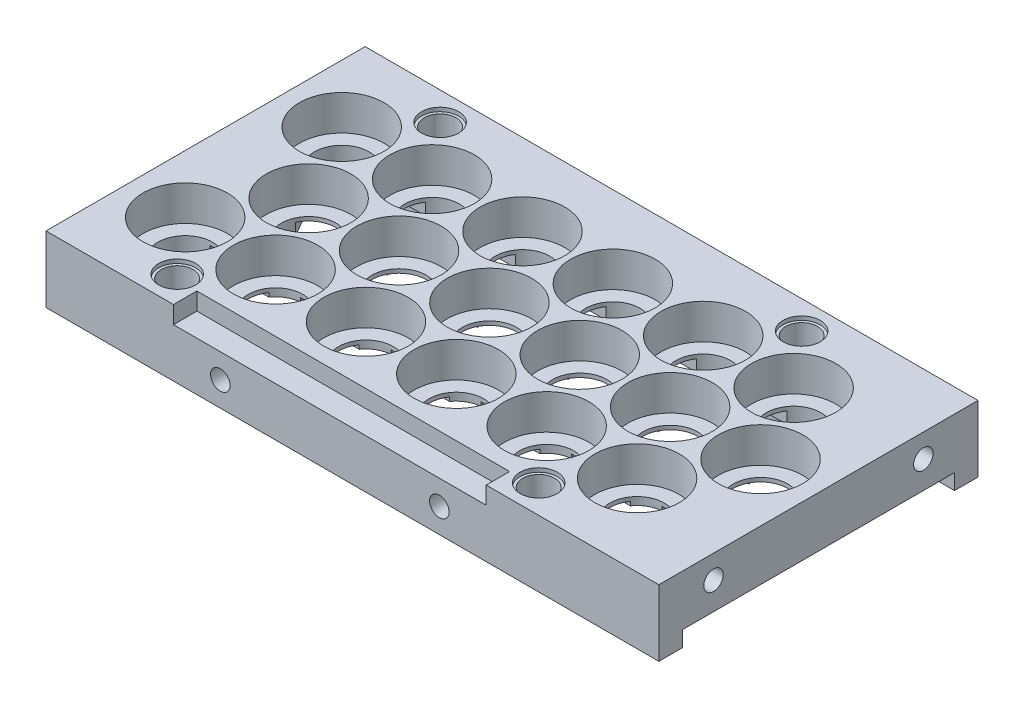
SolidWorks part; units mm, degrees
ref_plane "Front Plane" through (0, 0, 0) normal (0, 0, 1) x (1, 0, 0)
ref_plane "Top Plane" through (0, 0, 0) normal (0, 1, 0) x (1, 0, 0)
ref_plane "Right Plane" through (0, 0, 0) normal (1, 0, 0) x (0, 0, -1)
sketch "Sketch1" plane through (0, 0, 0) normal (0, 1, 0) x (1, 0, 0)
  line L0 (0, 0) -> (11.575, -20.0485) construction
  line L1 (11.575, -20.0485) -> (0, -40.097) construction
  line L2 (0, 0) -> (11.575, 0) construction
  line L3 (11.575, 0) -> (11.575, -20.0485) construction
  line L4 (11.575, -20.0485) -> (11.575, -40.097) construction
  line L5 (11.575, -40.097) -> (0, -40.097) construction
  line L6 (0, 0) -> (23.15, 0) construction
  line L7 (0, 0) -> (23.15, 0) construction
  line L8 (-14.825, -60.922) -> (142.15, -60.922)
  line L9 (-14.825, -60.922) -> (-14.825, 20.825)
  line L10 (-14.825, 20.825) -> (142.15, 20.825)
  line L11 (142.15, -60.922) -> (142.15, 20.825)
  circle A0 centre (0, 0) radius 10.825
  circle A1 centre (11.575, -20.0485) radius 10.825
  circle A2 centre (0, -40.097) radius 10.825
  circle A3 centre (23.15, 0) radius 10.825
  circle A4 centre (34.725, -20.0485) radius 10.825
  circle A5 centre (23.15, -40.097) radius 10.825
  circle A6 centre (46.3, 0) radius 10.825
  circle A7 centre (57.875, -20.0485) radius 10.825
  circle A8 centre (46.3, -40.097) radius 10.825
  circle A9 centre (69.45, 0) radius 10.825
  circle A10 centre (81.025, -20.0485) radius 10.825
  circle A11 centre (69.45, -40.097) radius 10.825
  circle A12 centre (92.6, 0) radius 10.825
  circle A13 centre (104.175, -20.0485) radius 10.825
  circle A14 centre (92.6, -40.097) radius 10.825
  circle A15 centre (115.75, 0) radius 10.825
  circle A16 centre (127.325, -20.0485) radius 10.825
  circle A17 centre (115.75, -40.097) radius 10.825
  circle A18 centre (0, 0) radius 7
  circle A19 centre (11.575, -20.0485) radius 7
  circle A20 centre (0, -40.097) radius 7
  circle A21 centre (23.15, 0) radius 7
  circle A22 centre (34.725, -20.0485) radius 7
  circle A23 centre (23.15, -40.097) radius 7
  circle A24 centre (46.3, 0) radius 7
  circle A25 centre (57.875, -20.0485) radius 7
  circle A26 centre (46.3, -40.097) radius 7
  circle A27 centre (69.45, 0) radius 7
  circle A28 centre (81.025, -20.0485) radius 7
  circle A29 centre (69.45, -40.097) radius 7
  circle A30 centre (92.6, 0) radius 7
  circle A31 centre (104.175, -20.0485) radius 7
  circle A32 centre (92.6, -40.097) radius 7
  circle A33 centre (115.75, 0) radius 7
  circle A34 centre (127.325, -20.0485) radius 7
  circle A35 centre (115.75, -40.097) radius 7
  dimension "D3" = 21.65
  dimension "D11" = 14
  dimension "D1" = 60
  dimension "D2" = 60
  dimension "D4" = 1.5
  dimension "D6" = 23.15
  dimension "D7" = 4
  dimension "D8" = 4
  dimension "D9" = 10
  dimension "D10" = 10
  dimension "D13" = 23.15
  dimension "D5" = 6
  dimension "D12" = 6
extrude "Boss-Extrude2" add sketch "Sketch1" along normal blind 11 contours L8 L11 L10 L9 A17 A16 A15 A14 A13 A12 A11 A10 A9 A8 A7 A6 A5 A4 A3 A2 A1 A0 region at (-13.0551, 0, 20.0485)
extrude "Boss-Extrude3" add sketch "Sketch1<3>" along normal blind 2 contours A0 A18 | A3 A21 | A6 A24 | A9 A27 | A12 A30 | A15 A33 | A1 A19 | A4 A22 | A7 A25 | A10 A28 | A13 A31 | A16 A34 | A17 A35 | A14 A32 | A11 A29 | A8 A26 | A5 A23 | A2 A20 region at (-10.5188, 0, 0) region at (1.0562, 0, 20.0485) region at (-10.5188, 0, 40.097) region at (12.6312, 0, 0) region at (24.2062, 0, 20.0485) region at (12.6312, 0, 40.097) region at (35.7812, 0, 0) region at (47.3562, 0, 20.0485) region at (35.7812, 0, 40.097) region at (58.9312, 0, 0) region at (70.5062, 0, 20.0485) region at (58.9312, 0, 40.097) region at (82.0812, 0, 0) region at (93.6562, 0, 20.0485) region at (82.0812, 0, 40.097) region at (105.2312, 0, 0) region at (116.8062, 0, 20.0485) region at (105.2312, 0, 40.097)
sketch "Sketch1<3>" plane through (0, 0, 0) normal (0, 1, 0) x (1, 0, 0) same geometry as "Sketch1"
sketch "Sketch2" plane through (0, 0, 0) normal (0, -1, 0) x (1, 0, 0)
  line L0 (0, 40.097) -> (11.575, 20.0485) construction
  line L1 (3.4641, 42.097) -> (15.0391, 22.0485)
  line L2 (-3.4641, 38.097) -> (8.1109, 18.0485)
  line L3 (11.575, 20.0485) -> (0, 0) construction
  line L4 (15.0391, 18.0485) -> (3.4641, -2)
  line L5 (8.1109, 22.0485) -> (-3.4641, 2)
  line L6 (19.6859, 38.097) -> (31.2609, 18.0485)
  line L7 (26.6141, 42.097) -> (38.1891, 22.0485)
  line L8 (31.2609, 22.0485) -> (19.6859, 2)
  line L9 (38.1891, 18.0485) -> (26.6141, -2)
  line L10 (23.15, 40.097) -> (34.725, 20.0485) construction
  line L11 (34.725, 20.0485) -> (23.15, 0) construction
  line L12 (42.8359, 38.097) -> (54.4109, 18.0485)
  line L13 (49.7641, 42.097) -> (61.3391, 22.0485)
  line L14 (54.4109, 22.0485) -> (42.8359, 2)
  line L15 (61.3391, 18.0485) -> (49.7641, -2)
  line L16 (46.3, 40.097) -> (57.875, 20.0485) construction
  line L17 (57.875, 20.0485) -> (46.3, 0) construction
  line L18 (65.9859, 38.097) -> (77.5609, 18.0485)
  line L19 (72.9141, 42.097) -> (84.4891, 22.0485)
  line L20 (77.5609, 22.0485) -> (65.9859, 2)
  line L21 (84.4891, 18.0485) -> (72.9141, -2)
  line L22 (69.45, 40.097) -> (81.025, 20.0485) construction
  line L23 (81.025, 20.0485) -> (69.45, 0) construction
  line L24 (89.1359, 38.097) -> (100.7109, 18.0485)
  line L25 (96.0641, 42.097) -> (107.6391, 22.0485)
  line L26 (100.7109, 22.0485) -> (89.1359, 2)
  line L27 (107.6391, 18.0485) -> (96.0641, -2)
  line L28 (92.6, 40.097) -> (104.175, 20.0485) construction
  line L29 (104.175, 20.0485) -> (92.6, 0) construction
  line L30 (112.2859, 38.097) -> (123.8609, 18.0485)
  line L31 (119.2141, 42.097) -> (130.7891, 22.0485)
  line L32 (123.8609, 22.0485) -> (112.2859, 2)
  line L33 (130.7891, 18.0485) -> (119.2141, -2)
  line L34 (115.75, 40.097) -> (127.325, 20.0485) construction
  line L35 (127.325, 20.0485) -> (115.75, 0) construction
  line L36 (-3.4641, 38.097) -> (19.6859, 38.097) construction
  line L37 (0, 40.097) -> (115.75, 40.097) construction
  line L38 (0, 44.097) -> (115.75, 44.097)
  line L39 (0, 36.097) -> (115.75, 36.097)
  line L40 (11.575, 20.0485) -> (127.325, 20.0485) construction
  line L41 (11.575, 24.0485) -> (127.325, 24.0485)
  line L42 (11.575, 16.0485) -> (127.325, 16.0485)
  line L43 (0, 0) -> (115.75, 0) construction
  line L44 (0, 4) -> (115.75, 4)
  line L45 (0, -4) -> (115.75, -4)
  arc A0 (3.4641, 42.097) -> (-3.4641, 38.097) centre (0, 40.097) ccw
  arc A1 (8.1109, 18.0485) -> (15.0391, 22.0485) centre (11.575, 20.0485) ccw
  arc A2 (15.0391, 18.0485) -> (8.1109, 22.0485) centre (11.575, 20.0485) ccw
  arc A3 (-3.4641, 2) -> (3.4641, -2) centre (0, 0) ccw
  arc A4 (26.6141, 42.097) -> (19.6859, 38.097) centre (23.15, 40.097) ccw
  arc A5 (31.2609, 18.0485) -> (38.1891, 22.0485) centre (34.725, 20.0485) ccw
  arc A6 (38.1891, 18.0485) -> (31.2609, 22.0485) centre (34.725, 20.0485) ccw
  arc A7 (19.6859, 2) -> (26.6141, -2) centre (23.15, 0) ccw
  arc A8 (49.7641, 42.097) -> (42.8359, 38.097) centre (46.3, 40.097) ccw
  arc A9 (54.4109, 18.0485) -> (61.3391, 22.0485) centre (57.875, 20.0485) ccw
  arc A10 (61.3391, 18.0485) -> (54.4109, 22.0485) centre (57.875, 20.0485) ccw
  arc A11 (42.8359, 2) -> (49.7641, -2) centre (46.3, 0) ccw
  arc A12 (72.9141, 42.097) -> (65.9859, 38.097) centre (69.45, 40.097) ccw
  arc A13 (77.5609, 18.0485) -> (84.4891, 22.0485) centre (81.025, 20.0485) ccw
  arc A14 (84.4891, 18.0485) -> (77.5609, 22.0485) centre (81.025, 20.0485) ccw
  arc A15 (65.9859, 2) -> (72.9141, -2) centre (69.45, 0) ccw
  arc A16 (96.0641, 42.097) -> (89.1359, 38.097) centre (92.6, 40.097) ccw
  arc A17 (100.7109, 18.0485) -> (107.6391, 22.0485) centre (104.175, 20.0485) ccw
  arc A18 (107.6391, 18.0485) -> (100.7109, 22.0485) centre (104.175, 20.0485) ccw
  arc A19 (89.1359, 2) -> (96.0641, -2) centre (92.6, 0) ccw
  arc A20 (119.2141, 42.097) -> (112.2859, 38.097) centre (115.75, 40.097) ccw
  arc A21 (123.8609, 18.0485) -> (130.7891, 22.0485) centre (127.325, 20.0485) ccw
  arc A22 (130.7891, 18.0485) -> (123.8609, 22.0485) centre (127.325, 20.0485) ccw
  arc A23 (112.2859, 2) -> (119.2141, -2) centre (115.75, 0) ccw
  arc A24 (0, 44.097) -> (0, 36.097) centre (0, 40.097) ccw
  arc A25 (115.75, 36.097) -> (115.75, 44.097) centre (115.75, 40.097) ccw
  arc A26 (11.575, 24.0485) -> (11.575, 16.0485) centre (11.575, 20.0485) ccw
  arc A27 (127.325, 16.0485) -> (127.325, 24.0485) centre (127.325, 20.0485) ccw
  arc A28 (0, 4) -> (0, -4) centre (0, 0) ccw
  arc A29 (115.75, -4) -> (115.75, 4) centre (115.75, 0) ccw
  point P3 (5.7875, 30.0727)
  point P8 (5.7875, 10.0242)
  point P18 (28.9375, 30.0727)
  point P25 (28.9375, 10.0242)
  point P34 (52.0875, 30.0727)
  point P39 (52.0875, 10.0242)
  point P48 (75.2375, 30.0727)
  point P53 (75.2375, 10.0242)
  point P62 (98.3875, 30.0727)
  point P67 (98.3875, 10.0242)
  point P76 (121.5375, 30.0727)
  point P81 (121.5375, 10.0242)
  point P91 (57.875, 40.097)
  point P96 (69.45, 20.0485)
  point P103 (57.875, 0)
  circle M62 centre (0, 0) radius 7
  circle M63 centre (23.15, 0) radius 7
  circle M64 centre (46.3, 0) radius 7
  circle M65 centre (69.45, 0) radius 7
  circle M66 centre (92.6, 0) radius 7
  circle M67 centre (115.75, 0) radius 7
  circle M68 centre (11.575, 20.0485) radius 7
  circle M69 centre (34.725, 20.0485) radius 7
  circle M70 centre (57.875, 20.0485) radius 7
  circle M71 centre (81.025, 20.0485) radius 7
  circle M72 centre (104.175, 20.0485) radius 7
  circle M73 centre (127.325, 20.0485) radius 7
  circle M74 centre (115.75, 40.097) radius 7
  circle M75 centre (92.6, 40.097) radius 7
  circle M76 centre (69.45, 40.097) radius 7
  circle M77 centre (46.3, 40.097) radius 7
  circle M78 centre (23.15, 40.097) radius 7
  circle M79 centre (0, 40.097) radius 7
  dimension "D1" = 8
  dimension "D3" = 23.15
  dimension "D4" = 8
  dimension "D5" = 8
  dimension "D6" = 8
extrude "Cut-Extrude1" cut sketch "Sketch2" against normal blind 1 contours L1 L39 L38 M78 M79 | L7 L39 L38 M77 M78 | L39 L2 L1 M79 M68 | L42 L8 L6 L41 M68 M69 | L6 L41 L7 L39 M69 M78 | L12 L41 L13 L39 M70 M77 | L13 L39 L38 M76 M77 | L18 L41 L19 L39 M71 M76 | L19 L39 L38 M75 M76 | L24 L41 L25 L39 M72 M75 | L25 L39 L38 M74 M75 | L30 L41 L31 M73 M74 | L42 L32 L30 L41 M72 M73 | L42 L26 L24 L41 M71 M72 | L42 L20 L18 L41 M70 M71 | L42 L14 L12 L41 M69 M70 | L45 L44 L4 M62 M63 | L44 L4 L5 M62 M68 | L45 L44 L9 M63 M64 | L45 L44 L15 M64 M65 | L45 L44 L21 M65 M66 | L45 L44 L27 M66 M67 | L44 L27 L42 L26 M66 M72 | L42 L32 L33 M67 M73 | L44 L21 L42 L20 M65 M71 | L44 L15 L42 L14 M64 M70 | L39 L13 M77 | L39 L25 M75 | L39 L19 M76 | L41 L6 M69 | L44 L4 M62 | L44 L15 M64 | L44 L21 M65 | L44 L27 M66 | L41 L30 M73 | L32 L42 M73 | L41 L24 M72 | L26 L42 M72 | L41 L18 M71 | L20 L42 M71 | L41 L12 M70 | L14 L42 M70 | L44 L9 L42 L8 M63 M69 | L8 L42 M69 | L39 L7 M78 | L39 L1 M79 | L44 A29 L45 A28 region at (11.6138, 0, 40.1242) region at (6.3461, 0, 36.4331) region at (5.7834, 0, 30.0255) region at (23.0718, 0, 20.0485) region at (28.9375, 0, 30.0727) region at (34.7638, 0, 40.1242) region at (28.3789, 0, 23.7124) region at (5.7834, 0, 10.0715) region at (29.4961, 0, 36.4331) region at (57.9138, 0, 40.1242) region at (28.3789, 0, 16.3846) region at (28.9375, 0, 10.0242) region at (6.3461, 0, 3.6639) region at (11.6138, 0, -0.0272) region at (52.0875, 0, 30.0727) region at (46.2218, 0, 20.0485) region at (52.6461, 0, 36.4331) region at (81.0638, 0, 40.1242) region at (51.5289, 0, 23.7124) region at (34.7638, 0, -0.0272) region at (75.2375, 0, 30.0727) region at (75.7961, 0, 36.4331) region at (104.2138, 0, 40.1242) region at (74.6789, 0, 23.7124) region at (69.3718, 0, 20.0485) region at (51.5289, 0, 16.3846) region at (52.0875, 0, 10.0242) region at (57.9138, 0, -0.0272) region at (98.3875, 0, 30.0727) region at (98.9461, 0, 36.4331) region at (97.8289, 0, 23.7124) region at (92.5218, 0, 20.0485) region at (74.6789, 0, 16.3846) region at (52.6461, 0, 3.6639) region at (81.0638, 0, -0.0272) region at (121.5416, 0, 30.12) region at (75.2375, 0, 10.0242) region at (120.9789, 0, 23.7124) region at (115.6718, 0, 20.0485) region at (97.8289, 0, 16.3846) region at (75.7961, 0, 3.6639) region at (104.2138, 0, -0.0272) region at (98.3875, 0, 10.0242) region at (121.5416, 0, 9.977) region at (120.9789, 0, 16.3846) region at (98.9461, 0, 3.6639)
sketch "Sketch9" plane through (0, 11, 0) normal (0, 1, 0) x (1, 0, 0)
  line L0 (11.575, -60.922) -> (11.575, 20.825)
  line L1 (-14.825, 20.825) -> (142.15, 20.825) construction
  line L2 (104.175, 20.825) -> (104.175, -60.922)
  line L3 (-14.825, -60.922) -> (142.15, -60.922) construction
  circle A0 centre (11.575, 13.625) radius 4.0767
  circle A1 centre (11.575, -53.722) radius 4.0767
  circle A2 centre (104.175, -53.722) radius 4.0767
  circle A3 centre (104.175, 13.625) radius 4.0767
  point P0 (11.575, 13.625)
  point P7 (11.575, -20.0485)
  point P15 (104.175, -20.0485)
  point P20 (104.175, 13.625)
  point P21 (104.175, -53.722)
  point P22 (11.575, -53.722)
  dimension "D5" = 8.1534
  dimension "D1" = 7.2
  dimension "D4" = 7.2
extrude "Cut-Extrude3" cut sketch "Sketch9" against normal up to next contours A2 | A1 | A0 | A3
sketch "Sketch10" plane through (0, 11, 0) normal (0, 1, 0) x (1, 0, 0)
  circle A0 centre (11.575, 13.625) radius 4.7625
  circle A1 centre (104.175, 13.625) radius 4.7625
  circle A2 centre (104.175, -53.722) radius 4.7625
  circle A3 centre (11.575, -53.722) radius 4.7625
  dimension "D1" = 9.525
extrude "Cut-Extrude4" cut sketch "Sketch10" against normal blind 1
sketch "Sketch13" plane through (0, 0, 0) normal (0, -1, 0) x (1, 0, 0)
  line L0 (142.15, 60.922) -> (142.15, -20.825) construction
  line L5 (3.575, 53.722) -> (3.575, 60.922)
  line L8 (-14.825, 60.922) -> (142.15, 60.922) construction
  line L9 (3.575, 60.922) -> (19.575, 60.922)
  line L10 (19.575, 60.922) -> (19.575, 53.722)
  line L12 (57.875, 20.0485) -> (57.875, -20.825) construction
  line L13 (-14.825, -20.825) -> (142.15, -20.825) construction
  line L14 (11.575, 20.0485) -> (127.325, 20.0485) construction
  line L16 (96.175, 60.922) -> (96.175, 53.722)
  line L17 (112.175, 60.922) -> (96.175, 60.922)
  line L18 (112.175, 53.722) -> (112.175, 60.922)
  line L19 (-14.825, 60.922) -> (142.15, 60.922)
  line L20 (-14.825, 60.922) -> (-14.825, 54.922)
  line L21 (-14.825, 54.922) -> (142.15, 54.922)
  line L22 (142.15, 60.922) -> (142.15, 54.922)
  line L23 (142.15, -20.825) -> (142.15, -14.825)
  line L24 (-14.825, -14.825) -> (142.15, -14.825)
  line L25 (-14.825, -20.825) -> (-14.825, -14.825)
  line L26 (-14.825, -20.825) -> (142.15, -20.825)
  line L27 (112.175, -13.625) -> (112.175, -20.825)
  line L28 (112.175, -20.825) -> (96.175, -20.825)
  line L29 (96.175, -20.825) -> (96.175, -13.625)
  line L32 (19.575, -20.825) -> (19.575, -13.625)
  line L33 (3.575, -20.825) -> (19.575, -20.825)
  line L34 (3.575, -13.625) -> (3.575, -20.825)
  circle A4 centre (11.575, 53.722) radius 6.5
  circle A5 centre (11.575, 53.722) radius 8
  circle A6 centre (104.175, 53.722) radius 8
  circle A7 centre (104.175, 53.722) radius 6.5
  circle A8 centre (104.175, -13.625) radius 6.5
  circle A9 centre (104.175, -13.625) radius 8
  circle A10 centre (11.575, -13.625) radius 8
  circle A11 centre (11.575, -13.625) radius 6.5
  line M15 (142.15, 60.922) -> (-14.825, 60.922)
  line M16 (-14.825, 60.922) -> (-14.825, -20.825)
  line M17 (-14.825, -20.825) -> (142.15, -20.825)
  line M18 (142.15, -20.825) -> (142.15, 60.922)
  dimension "D1" = 13
  dimension "D2" = 16
  dimension "D3" = 6
extrude "Boss-Extrude7" add sketch "Sketch13" along normal blind 6 contours L21 L5 M16 M15 | A5 L5 L21 M15 | A5 L21 L10 M15 | L10 L21 L16 M15 | L21 A5 L19 A4 | A5 L21 A4 | L21 A6 L16 M15 | L21 A7 A6 L19 | L21 A7 A6 | A6 L21 L18 M15 | L18 L21 M18 M15 | A9 L24 L29 L26 | L28 A9 L24 A8 | A9 L26 L27 L24 | L24 L27 L26 M18 | L32 L26 L29 L24 | L24 A9 A8 | L34 L24 M16 M17 | L26 A10 L24 L34 | L24 A11 A10 | L24 A11 A10 L33 | L24 A10 L26 L32 region at (3.7817, 0, 54.3098) region at (-5.625, 0, 57.922) region at (4.8282, 0, 59.2567) region at (5.2714, 0, 58.3681) region at (18.3218, 0, 59.2567) region at (57.875, 0, 57.922) region at (-5.625, 0, -17.825) region at (97.4282, 0, 59.2567) region at (4.8282, 0, -19.1597) region at (96.3817, 0, 54.3098) region at (97.8714, 0, 58.3681) region at (3.7817, 0, -14.2128) region at (4.4261, 0, -14.9942) region at (110.9218, 0, 59.2567) region at (127.1625, 0, 57.922) region at (18.3218, 0, -19.1597) region at (57.875, 0, -17.825) region at (97.4282, 0, -19.1597) region at (127.1625, 0, -17.825) region at (96.3817, 0, -14.2128) region at (97.0261, 0, -14.9942) region at (110.9218, 0, -19.1597)
sketch "Sketch14" plane through (0, 0, 0) normal (0, -1, 0) x (1, 0, 0)
  line L2 (142.15, 54.922) -> (142.15, -14.825) construction
  line L4 (5.2386, 17.0736) -> (-0.5918, 6.9749) construction
  line L5 (5.7446, -4) -> (17.4054, -4) construction
  line L6 (28.8946, -4) -> (40.5554, -4) construction
  line L7 (52.0446, -4) -> (63.7054, -4) construction
  line L8 (75.1946, -4) -> (86.8554, -4) construction
  line L9 (98.3446, -4) -> (110.0054, -4) construction
  line L10 (127.9168, 13.0736) -> (122.0864, 2.9749) construction
  line L11 (122.0864, 37.122) -> (127.9168, 27.0234) construction
  line L12 (98.3446, 44.097) -> (110.0054, 44.097) construction
  line L13 (75.1946, 44.097) -> (86.8554, 44.097) construction
  line L14 (52.0446, 44.097) -> (63.7054, 44.097) construction
  line L15 (28.8946, 44.097) -> (40.5554, 44.097) construction
  line L16 (-0.5918, 33.122) -> (5.2386, 23.0234) construction
  line L17 (5.7446, 44.097) -> (17.4054, 44.097) construction
  line L20 (142.15, 54.922) -> (142.15, -14.825)
  line L22 (5.2386, 17.0736) -> (-0.5918, 6.9749)
  line L23 (5.7446, -4) -> (17.4054, -4)
  line L24 (28.8946, -4) -> (40.5554, -4)
  line L25 (52.0446, -4) -> (63.7054, -4)
  line L26 (75.1946, -4) -> (86.8554, -4)
  line L27 (98.3446, -4) -> (110.0054, -4)
  line L28 (127.9168, 13.0736) -> (122.0864, 2.9749)
  line L29 (122.0864, 37.122) -> (127.9168, 27.0234)
  line L30 (98.3446, 44.097) -> (110.0054, 44.097)
  line L31 (75.1946, 44.097) -> (86.8554, 44.097)
  line L32 (52.0446, 44.097) -> (63.7054, 44.097)
  line L33 (28.8946, 44.097) -> (40.5554, 44.097)
  line L34 (-0.5918, 33.122) -> (5.2386, 23.0234)
  line L35 (5.7446, 44.097) -> (17.4054, 44.097)
  line L36 (112.0845, -14.825) -> (142.15, -14.825) construction
  line L37 (19.4845, -14.825) -> (96.2655, -14.825) construction
  line L38 (-14.825, -14.825) -> (3.6655, -14.825) construction
  line L39 (-14.825, 54.922) -> (-14.825, -14.825) construction
  line L40 (112.0845, 54.922) -> (142.15, 54.922) construction
  line L41 (19.4845, 54.922) -> (96.2655, 54.922) construction
  line L42 (-14.825, 54.922) -> (3.6655, 54.922) construction
  line L43 (112.0845, -14.825) -> (142.15, -14.825)
  line L44 (19.4845, -14.825) -> (96.2655, -14.825)
  line L45 (-14.825, -14.825) -> (3.6655, -14.825)
  line L46 (-14.825, 54.922) -> (-14.825, -14.825)
  line L47 (112.0845, 54.922) -> (142.15, 54.922)
  line L48 (19.4845, 54.922) -> (96.2655, 54.922)
  line L49 (-14.825, 54.922) -> (3.6655, 54.922)
  arc A3 (5.2386, 23.0234) -> (5.2386, 17.0736) centre (11.575, 20.0485) ccw construction
  arc A4 (-0.5918, 6.9749) -> (5.7446, -4) centre (0, 0) ccw construction
  arc A5 (17.4054, -4) -> (28.8946, -4) centre (23.15, 0) ccw construction
  arc A6 (40.5554, -4) -> (52.0446, -4) centre (46.3, 0) ccw construction
  arc A7 (63.7054, -4) -> (75.1946, -4) centre (69.45, 0) ccw construction
  arc A8 (86.8554, -4) -> (98.3446, -4) centre (92.6, 0) ccw construction
  arc A9 (110.0054, -4) -> (122.0864, 2.9749) centre (115.75, 0) ccw construction
  arc A10 (127.9168, 13.0736) -> (127.9168, 27.0234) centre (127.325, 20.0485) ccw construction
  arc A11 (122.0864, 37.122) -> (110.0054, 44.097) centre (115.75, 40.097) ccw construction
  arc A12 (98.3446, 44.097) -> (86.8554, 44.097) centre (92.6, 40.097) ccw construction
  arc A13 (75.1946, 44.097) -> (63.7054, 44.097) centre (69.45, 40.097) ccw construction
  arc A14 (52.0446, 44.097) -> (40.5554, 44.097) centre (46.3, 40.097) ccw construction
  arc A16 (28.8946, 44.097) -> (17.4054, 44.097) centre (23.15, 40.097) ccw construction
  arc A17 (5.7446, 44.097) -> (-0.5918, 33.122) centre (0, 40.097) ccw construction
  arc A21 (5.2386, 23.0234) -> (5.2386, 17.0736) centre (11.575, 20.0485) ccw
  arc A22 (-0.5918, 6.9749) -> (5.7446, -4) centre (0, 0) ccw
  arc A23 (17.4054, -4) -> (28.8946, -4) centre (23.15, 0) ccw
  arc A24 (40.5554, -4) -> (52.0446, -4) centre (46.3, 0) ccw
  arc A25 (63.7054, -4) -> (75.1946, -4) centre (69.45, 0) ccw
  arc A26 (86.8554, -4) -> (98.3446, -4) centre (92.6, 0) ccw
  arc A27 (110.0054, -4) -> (122.0864, 2.9749) centre (115.75, 0) ccw
  arc A28 (127.9168, 13.0736) -> (127.9168, 27.0234) centre (127.325, 20.0485) ccw
  arc A29 (122.0864, 37.122) -> (110.0054, 44.097) centre (115.75, 40.097) ccw
  arc A30 (98.3446, 44.097) -> (86.8554, 44.097) centre (92.6, 40.097) ccw
  arc A31 (75.1946, 44.097) -> (63.7054, 44.097) centre (69.45, 40.097) ccw
  arc A32 (52.0446, 44.097) -> (40.5554, 44.097) centre (46.3, 40.097) ccw
  arc A34 (28.8946, 44.097) -> (17.4054, 44.097) centre (23.15, 40.097) ccw
  arc A35 (5.7446, 44.097) -> (-0.5918, 33.122) centre (0, 40.097) ccw
  arc A36 (112.0845, -14.825) -> (96.2655, -14.825) centre (104.175, -13.625) ccw construction
  arc A37 (19.4845, -14.825) -> (3.6655, -14.825) centre (11.575, -13.625) ccw construction
  arc A38 (96.2655, 54.922) -> (112.0845, 54.922) centre (104.175, 53.722) ccw construction
  arc A39 (3.6655, 54.922) -> (19.4845, 54.922) centre (11.575, 53.722) ccw construction
  arc A40 (112.0845, -14.825) -> (96.2655, -14.825) centre (104.175, -13.625) ccw
  arc A41 (19.4845, -14.825) -> (3.6655, -14.825) centre (11.575, -13.625) ccw
  arc A42 (96.2655, 54.922) -> (112.0845, 54.922) centre (104.175, 53.722) ccw
  arc A43 (3.6655, 54.922) -> (19.4845, 54.922) centre (11.575, 53.722) ccw
extrude "Boss-Extrude9" add sketch "Sketch14" along normal blind 2
sketch "Sketch16" plane through (0, 0, 0) normal (0, -1, 0) x (1, 0, 0)
  line L0 (17.4054, 36.097) -> (12.1668, 27.0234) construction
  line L1 (12.1668, 27.0234) -> (17.3196, 24.0485) construction
  line L2 (17.3196, 24.0485) -> (22.5582, 33.122) construction
  line L3 (22.5582, 33.122) -> (17.4054, 36.097) construction
  line L4 (14.7861, 31.5602) -> (19.9389, 28.5853) construction
  line L5 (15.5361, 32.8592) -> (20.6889, 29.8843)
  line L6 (14.0361, 30.2612) -> (19.1889, 27.2862)
  line L7 (11.575, 20.0485) -> (126.446, 20.0485) construction
  line L8 (40.5554, 36.097) -> (35.3168, 27.0234) construction
  line L9 (35.3168, 27.0234) -> (40.4696, 24.0485) construction
  line L10 (40.4696, 24.0485) -> (45.7082, 33.122) construction
  line L11 (45.7082, 33.122) -> (40.5554, 36.097) construction
  line L12 (37.9361, 31.5602) -> (43.0889, 28.5853) construction
  line L13 (38.6861, 32.8592) -> (43.8389, 29.8843)
  line L14 (37.1861, 30.2612) -> (42.3389, 27.2862)
  line L15 (63.7054, 36.097) -> (58.4668, 27.0234) construction
  line L16 (58.4668, 27.0234) -> (63.6196, 24.0485) construction
  line L17 (63.6196, 24.0485) -> (68.8582, 33.122) construction
  line L18 (68.8582, 33.122) -> (63.7054, 36.097) construction
  line L19 (61.0861, 31.5602) -> (66.2389, 28.5853) construction
  line L20 (61.8361, 32.8592) -> (66.9889, 29.8843)
  line L21 (60.3361, 30.2612) -> (65.4889, 27.2862)
  line L22 (86.8554, 36.097) -> (81.6168, 27.0234) construction
  line L23 (81.6168, 27.0234) -> (86.7696, 24.0485) construction
  line L24 (86.7696, 24.0485) -> (92.0082, 33.122) construction
  line L25 (92.0082, 33.122) -> (86.8554, 36.097) construction
  line L26 (84.2361, 31.5602) -> (89.3889, 28.5853) construction
  line L27 (84.9861, 32.8592) -> (90.1389, 29.8843)
  line L28 (83.4861, 30.2612) -> (88.6389, 27.2862)
  line L29 (110.0054, 36.097) -> (104.7668, 27.0234) construction
  line L30 (104.7668, 27.0234) -> (109.9196, 24.0485) construction
  line L31 (109.9196, 24.0485) -> (115.1582, 33.122) construction
  line L32 (115.1582, 33.122) -> (110.0054, 36.097) construction
  line L33 (107.3861, 31.5602) -> (112.5389, 28.5853) construction
  line L34 (108.1361, 32.8592) -> (113.2889, 29.8843)
  line L35 (106.6361, 30.2612) -> (111.7889, 27.2862)
  line L36 (14.7861, 8.5368) -> (19.9389, 11.5117) construction
  line L37 (15.5361, 7.2377) -> (20.6889, 10.2127)
  line L38 (14.0361, 9.8358) -> (19.1889, 12.8108)
  line L39 (37.9361, 8.5368) -> (43.0889, 11.5117) construction
  line L40 (38.6861, 7.2377) -> (43.8389, 10.2127)
  line L41 (37.1861, 9.8358) -> (42.3389, 12.8108)
  line L42 (61.0861, 8.5368) -> (66.2389, 11.5117) construction
  line L43 (61.8361, 7.2377) -> (66.9889, 10.2127)
  line L44 (60.3361, 9.8358) -> (65.4889, 12.8108)
  line L45 (84.2361, 8.5368) -> (89.3889, 11.5117) construction
  line L46 (84.9861, 7.2377) -> (90.1389, 10.2127)
  line L47 (83.4861, 9.8358) -> (88.6389, 12.8108)
  line L48 (107.3861, 8.5368) -> (112.5389, 11.5117) construction
  line L49 (108.1361, 7.2377) -> (113.2889, 10.2127)
  line L50 (106.6361, 9.8358) -> (111.7889, 12.8108)
  line L51 (115.1582, 6.9749) -> (110.0054, 4) construction
  line L52 (109.9196, 16.0485) -> (115.1582, 6.9749) construction
  line L53 (104.7668, 13.0736) -> (109.9196, 16.0485) construction
  line L54 (110.0054, 4) -> (104.7668, 13.0736) construction
  line L55 (92.0082, 6.9749) -> (86.8554, 4) construction
  line L56 (86.7696, 16.0485) -> (92.0082, 6.9749) construction
  line L57 (81.6168, 13.0736) -> (86.7696, 16.0485) construction
  line L58 (86.8554, 4) -> (81.6168, 13.0736) construction
  line L59 (68.8582, 6.9749) -> (63.7054, 4) construction
  line L60 (63.6196, 16.0485) -> (68.8582, 6.9749) construction
  line L61 (58.4668, 13.0736) -> (63.6196, 16.0485) construction
  line L62 (63.7054, 4) -> (58.4668, 13.0736) construction
  line L63 (45.7082, 6.9749) -> (40.5554, 4) construction
  line L64 (40.4696, 16.0485) -> (45.7082, 6.9749) construction
  line L65 (35.3168, 13.0736) -> (40.4696, 16.0485) construction
  line L66 (40.5554, 4) -> (35.3168, 13.0736) construction
  line L67 (22.5582, 6.9749) -> (17.4054, 4) construction
  line L68 (17.3196, 16.0485) -> (22.5582, 6.9749) construction
  line L69 (12.1668, 13.0736) -> (17.3196, 16.0485) construction
  line L70 (17.4054, 4) -> (12.1668, 13.0736) construction
  arc A0 (15.5361, 32.8592) -> (14.0361, 30.2612) centre (14.7861, 31.5602) ccw
  arc A1 (19.1889, 27.2862) -> (20.6889, 29.8843) centre (19.9389, 28.5853) ccw
  arc A2 (38.6861, 32.8592) -> (37.1861, 30.2612) centre (37.9361, 31.5602) ccw
  arc A3 (42.3389, 27.2862) -> (43.8389, 29.8843) centre (43.0889, 28.5853) ccw
  arc A4 (61.8361, 32.8592) -> (60.3361, 30.2612) centre (61.0861, 31.5602) ccw
  arc A5 (65.4889, 27.2862) -> (66.9889, 29.8843) centre (66.2389, 28.5853) ccw
  arc A6 (84.9861, 32.8592) -> (83.4861, 30.2612) centre (84.2361, 31.5602) ccw
  arc A7 (88.6389, 27.2862) -> (90.1389, 29.8843) centre (89.3889, 28.5853) ccw
  arc A8 (108.1361, 32.8592) -> (106.6361, 30.2612) centre (107.3861, 31.5602) ccw
  arc A9 (111.7889, 27.2862) -> (113.2889, 29.8843) centre (112.5389, 28.5853) ccw
  arc A10 (40.5554, 36.097) -> (45.7082, 33.122) centre (46.3, 40.097) ccw construction
  arc A11 (15.5361, 7.2377) -> (14.0361, 9.8358) centre (14.7861, 8.5368) cw
  arc A12 (19.1889, 12.8108) -> (20.6889, 10.2127) centre (19.9389, 11.5117) cw
  arc A13 (38.6861, 7.2377) -> (37.1861, 9.8358) centre (37.9361, 8.5368) cw
  arc A14 (42.3389, 12.8108) -> (43.8389, 10.2127) centre (43.0889, 11.5117) cw
  arc A15 (61.8361, 7.2377) -> (60.3361, 9.8358) centre (61.0861, 8.5368) cw
  arc A16 (65.4889, 12.8108) -> (66.9889, 10.2127) centre (66.2389, 11.5117) cw
  arc A17 (84.9861, 7.2377) -> (83.4861, 9.8358) centre (84.2361, 8.5368) cw
  arc A18 (88.6389, 12.8108) -> (90.1389, 10.2127) centre (89.3889, 11.5117) cw
  arc A19 (108.1361, 7.2377) -> (106.6361, 9.8358) centre (107.3861, 8.5368) cw
  arc A20 (111.7889, 12.8108) -> (113.2889, 10.2127) centre (112.5389, 11.5117) cw
  point P10 (17.3625, 30.0727)
  point P25 (40.5125, 30.0727)
  point P36 (63.6625, 30.0727)
  point P47 (86.8125, 30.0727)
  point P58 (109.9625, 30.0727)
  point P68 (17.3625, 10.0242)
  point P75 (40.5125, 10.0242)
  point P82 (63.6625, 10.0242)
  point P89 (86.8125, 10.0242)
  point P96 (109.9625, 10.0242)
  dimension "D1" = 1.5
  dimension "D2" = 5
extrude "Boss-Extrude10" add sketch "Sketch16" along normal blind 2
sketch "Sketch17" plane through (0, -2, 0) normal (0, -1, 0) x (-1, 0, 0)
  line L0 (-57.875, -44.097) -> (-57.875, -54.922) construction
  line L1 (-63.7054, -44.097) -> (-52.0446, -44.097) construction
  line L2 (-19.4845, -54.922) -> (-96.2655, -54.922) construction
  line L3 (-142.15, 14.825) -> (-142.15, -54.922) construction
  line L4 (14.825, -54.922) -> (14.825, 14.825) construction
  line L5 (10.825, -49.5095) -> (-57.875, -49.5095) construction
  line L6 (-57.875, -49.5095) -> (-132.15, -49.5095) construction
  line L7 (-127.325, -20.0485) -> (-11.575, -20.0485)
  line L8 (-57.875, 9.4125) -> (-132.15, 9.4125) construction
  line L9 (10.825, 9.4125) -> (-57.875, 9.4125) construction
  line L10 (-57.875, 4) -> (-57.875, 14.825) construction
  circle A0 centre (10.825, -49.5095) radius 2.5
  circle A1 centre (-57.875, -49.5095) radius 2.5
  circle A2 centre (-132.15, -49.5095) radius 2.5
  circle A3 centre (-132.15, 9.4125) radius 2.5
  circle A4 centre (-57.875, 9.4125) radius 2.5
  circle A5 centre (10.825, 9.4125) radius 2.5
  dimension "D1" = 5
  dimension "D2" = 10
  dimension "D3" = 4
extrude "Cut-Extrude5" cut sketch "Sketch17" against normal blind 4 contours A3 | A2 | A4 | A5 | A0 | A1 region at (-10.825, -2, 49.5095) region at (57.875, -2, 49.5095) region at (132.15, -2, 49.5095) region at (132.15, -2, -9.4125) region at (57.875, -2, -9.4125) region at (-10.825, -2, -9.4125)
sketch "Sketch19" plane through (0, 0, 60.922) normal (0, 0, 1) x (1, 0, 0)
  line L0 (11.575, 11) -> (104.175, 11)
  line L1 (-14.825, 11) -> (142.15, 11) construction
  line L2 (97.925, 11) -> (17.825, 11)
  line L3 (17.825, 11) -> (97.925, 11)
  line L4 (17.825, 11) -> (17.825, 6.525)
  line L5 (97.925, 11) -> (97.925, 6.525)
  line L6 (17.825, 6.525) -> (97.925, 6.525)
  point P5 (57.875, 11)
  point P9 (57.875, 11)
  dimension "D1" = 92.6
  dimension "D2" = 26.4
  dimension "D3" = 80.1
  dimension "D4" = 4.475
extrude "Cut-Extrude6" cut sketch "Sketch19" against normal blind 6 contours L4 L6 L5 L0 region at (57.875, 8.7625, 60.922)
sketch "Sketch20" plane through (0, 0, 60.922) normal (0, 0, 1) x (1, 0, 0)
  line L0 (29.825, 6.525) -> (85.925, 6.525)
  line L1 (29.825, 6.525) -> (29.825, 0.2625)
  line L2 (85.925, 6.525) -> (85.925, 0.2625)
  line L3 (29.825, 0.2625) -> (85.925, 0.2625)
  line L4 (29.825, 6.525) -> (17.825, 6.525) construction
  line L5 (85.925, 6.525) -> (97.925, 6.525) construction
  line L6 (57.875, 6.525) -> (57.875, -6)
  line L9 (142.15, -6) -> (-14.825, -6) construction
  circle A0 centre (29.825, 0.2625) radius 2.5
  circle A1 centre (85.925, 0.2625) radius 2.5
  point P9 (57.875, 0.2625)
  dimension "D2" = 5
  dimension "D1" = 12
extrude "Cut-Extrude7" cut sketch "Sketch20" against normal blind 5 contours L1 A0 L3 | L3 A0 L1 | L3 A1 L2 | L2 A1 L3 region at (30.886, 1.3235, 60.922) region at (29.4713, -0.0912, 60.922) region at (86.2787, -0.0912, 60.922) region at (84.864, 1.3235, 60.922)
sketch "Sketch22" plane through (142.15, 0, 0) normal (1, 0, 0) x (0, 0, -1)
  line L0 (-46.922, 5) -> (-60.922, 5)
  line L1 (-60.922, 11) -> (-60.922, -6) construction
  line L2 (6.825, 5) -> (20.825, 5)
  line L3 (20.825, 11) -> (20.825, -6) construction
  line L4 (-46.922, 5) -> (-46.922, 11)
  line L5 (-60.922, 11) -> (20.825, 11) construction
  line L6 (6.825, 5) -> (6.825, 11)
  circle A0 centre (-46.922, 5) radius 2.5
  circle A1 centre (6.825, 5) radius 2.5
  dimension "D1" = 5
  dimension "D2" = 14
  dimension "D3" = 6
extrude "Cut-Extrude8" cut sketch "Sketch22" against normal blind 10 contours L0 A0 L4 | L4 A0 L0 | L6 A1 L2 | L2 A1 L6 region at (142.15, 4.6463, 46.5683) region at (142.15, 6.061, 47.983) region at (142.15, 6.061, -7.886) region at (142.15, 4.6463, -6.4713)
equation "\"hole_diameter\"= 21.65"
equation "\"D3@Sketch1\"=\"hole_diameter\""
equation "\"cell_spacing\"= 1.5"
equation "\"D4@Sketch1\"=\"cell_spacing\""
equation "\"D6@Sketch1\"=\"hole_diameter\"+\"cell_spacing\""
equation "\"len_spacing\"= 4"
equation "\"D7@Sketch1\"=\"len_spacing\""
equation "\"D8@Sketch1\"=\"len_spacing\""
equation "\"wid_spacing\"= 10"
equation "\"D9@Sketch1\"=\"wid_spacing\""
equation "\"D10@Sketch1\"=\"wid_spacing\""
equation "\"nipple\"= 14"
equation "\"D11@Sketch1\"=\"nipple\""
equation "\"D13@Sketch1\"=\"hole_diameter\"+\"cell_spacing\""
equation "\"channel\"= 8"
equation "\"D1@Sketch2\"=\"channel\""
equation "\"D3@Sketch2\"=\"hole_diameter\"+\"cell_spacing\""
equation "\"D4@Sketch2\"=\"channel\""
equation "\"D5@Sketch2\"=\"channel\""
equation "\"D6@Sketch2\"=\"channel\""
equation "\"lip\"= 6"
equation "\"lip_height\"= 1"
equation "\"outer_fillet\"=6"
equation "\"insert_placement\"= 7.2"
equation "\"D4@Sketch9\"=\"insert_placement\""
equation "\"D1@Sketch9\"=\"insert_placement\""
equation "\"heat_insert_diameter\"=8.1534"
equation "\"D5@Sketch9\"=\"heat_insert_diameter\""
equation "\"heat_insert_lip_diameter\"=9.525"
equation "\"D1@Sketch10\"=\"heat_insert_lip_diameter\""
equation "\"bolt_head_diameter\"=13"
equation "\"D1@Sketch13\"=\"bolt_head_diameter\""
equation "\"D2@Sketch13\"=\"bolt_head_diameter\"+3"
equation "\"D3@Sketch13\"=\"lip\""
equation "\"small_heat_insert\"=5"
equation "\"D1@Sketch17\"=\"small_heat_insert\""
equation "\"bdm_cut_depth\"=6"
equation "\"D1@Cut-Extrude6\"=\"bdm_cut_depth\""
equation "\"D1@Cut-Extrude7\"=\"small_heat_insert\""
equation "\"D2@Sketch20\"=\"small_heat_insert\""
equation "\"heat_insert_space\"=6"
equation "\"heat_insert\"=5.5"
